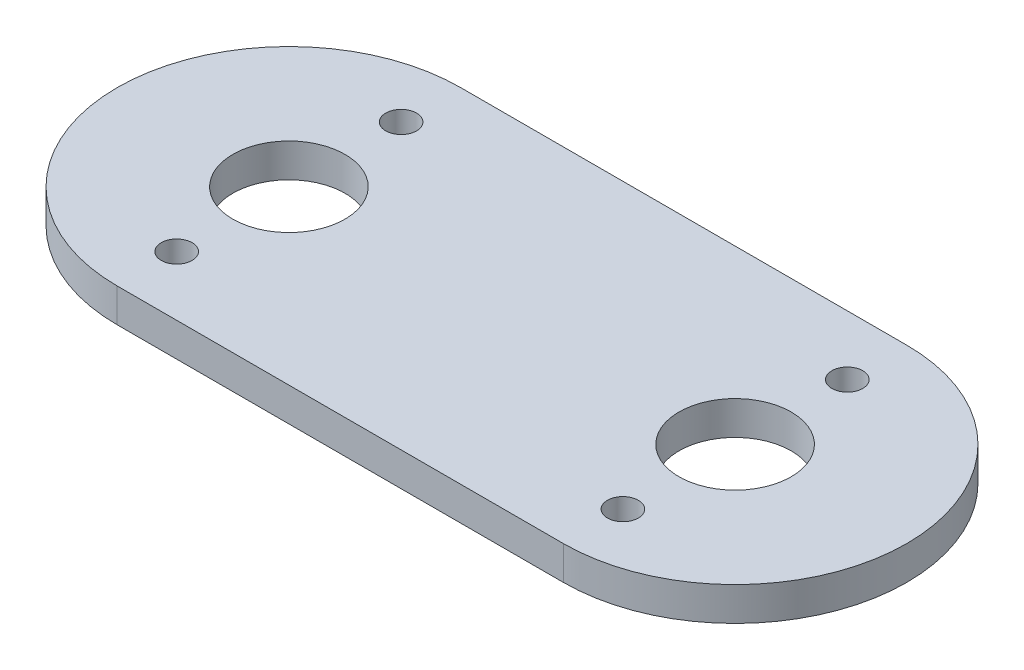
SolidWorks part; units mm, degrees
ref_plane "Front Plane" through (0, 0, 0) normal (0, 0, 1) x (1, 0, 0)
ref_plane "Top Plane" through (0, 0, 0) normal (0, 1, 0) x (1, 0, 0)
ref_plane "Right Plane" through (0, 0, 0) normal (1, 0, 0) x (0, 0, -1)
sketch "Sketch1" plane through (0, 0, 0) normal (0, 1, 0) x (1, 0, 0)
  line L0 (-31.9723, 0) -> (7.786, 0)
  line L1 (7.786, -30.6106) -> (-31.9723, -30.6106)
  arc A0 (7.786, 0) -> (7.786, -30.6106) centre (7.786, -15.3053) cw
  arc A1 (-31.9723, -30.6106) -> (-31.9723, 0) centre (-31.9723, -15.3053) cw
  dimension "D1" = 39.7583
  dimension "D2" = 30.6106
extrude "Boss-Extrude1" add sketch "Sketch1" along normal blind 3
sketch "Sketch2" plane through (0, 3, 0) normal (0, 1, 0) x (1, 0, 0)
  line L0 (-12.0932, -54.7734) -> (-12.0932, 0) construction
  line L1 (-31.9723, 0) -> (-31.9723, -30.6106) construction
  line L2 (-54.6054, -15.3053) -> (-12.0932, -15.3053) construction
  line L3 (7.786, 0) -> (-31.9723, 0) construction
  circle A0 centre (-31.9723, -15.3053) radius 5
  circle A1 centre (-31.9723, -5.3053) radius 1.375
  circle A2 centre (-31.9723, -25.3053) radius 1.375
  circle A3 centre (7.786, -5.3053) radius 1.375
  circle A4 centre (7.786, -15.3053) radius 5
  circle A5 centre (7.786, -25.3053) radius 1.375
  point P23 (-12.0932, 0)
  dimension "D1" = 10
  dimension "D2" = 2.75
  dimension "D3" = 10
extrude "Cut-Extrude1" cut sketch "Sketch2" against normal through all
